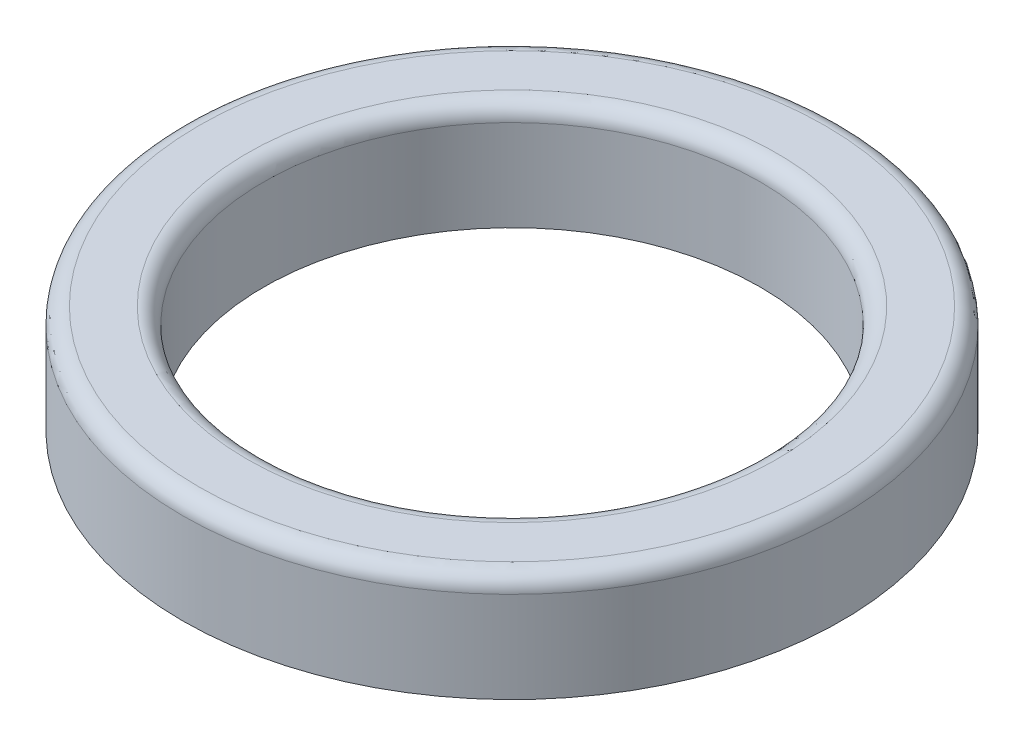
SolidWorks part; units mm, degrees
ref_plane "Front Plane" through (0, 0, 0) normal (0, 0, 1) x (1, 0, 0)
ref_plane "Top Plane" through (0, 0, 0) normal (0, 1, 0) x (1, 0, 0)
ref_plane "Right Plane" through (0, 0, 0) normal (1, 0, 0) x (0, 0, -1)
sketch "Sketch1" plane through (0, 0, 0) normal (0, 1, 0) x (1, 0, 0)
  circle A0 centre (0, 0) radius 15
  circle A1 centre (0, 0) radius 19.9
  dimension "D1" = 30
  dimension "D2" = 39.8
extrude "Boss-Extrude2" add sketch "Sketch1" along normal blind 6.5
fillet "Fillet1" radius 1 2 edges at (0, 6.5, 15) (0, 6.5, 19.9)
